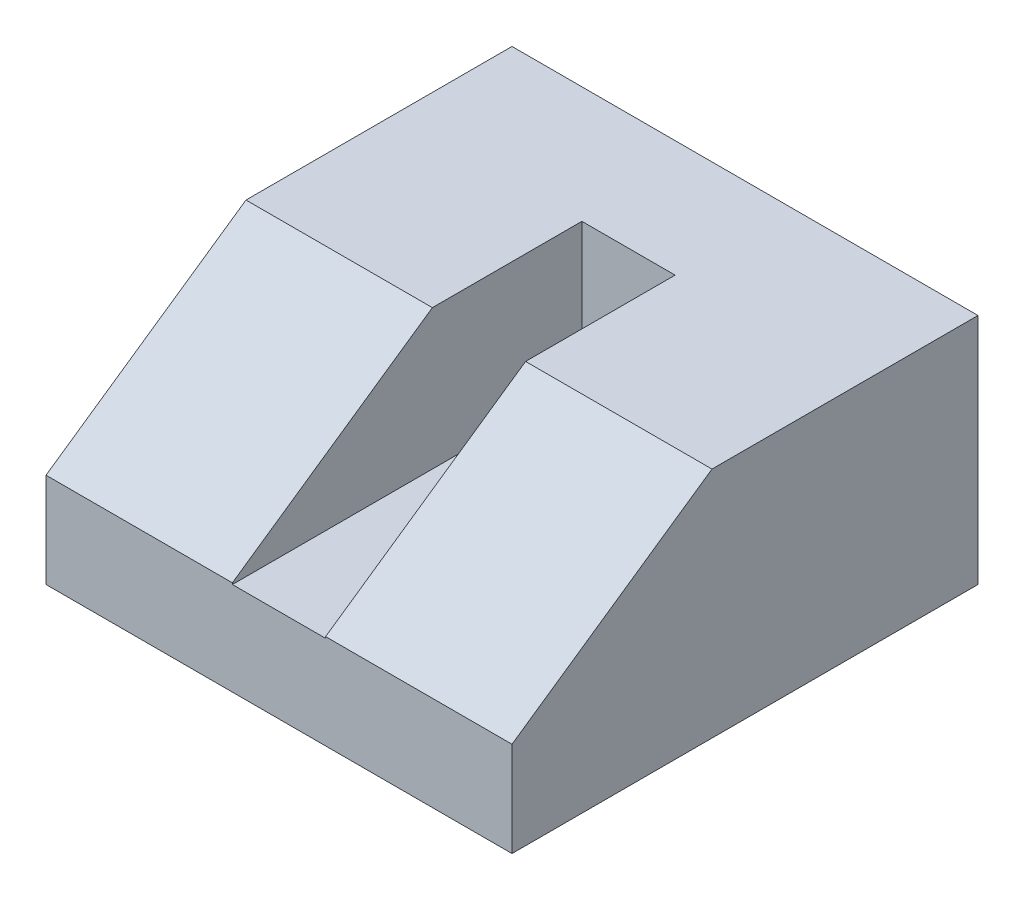
SolidWorks part; units mm, degrees
ref_plane "Front Plane" through (0, 0, 0) normal (0, 0, 1) x (1, 0, 0)
ref_plane "Top Plane" through (0, 0, 0) normal (0, 1, 0) x (1, 0, 0)
ref_plane "Right Plane" through (0, 0, 0) normal (1, 0, 0) x (0, 0, -1)
sketch "Sketch1" plane through (0, 0, 0) normal (0, 1, 0) x (1, 0, 0)
  circle A0 centre (0, 0) radius 25
  dimension "D1" = 50
extrude "Boss-Extrude1" add sketch "Sketch1" along normal blind 10
sketch "Sketch2" plane through (0, 10, 0) normal (0, 1, 0) x (1, 0, 0)
  line L1 (50, -50) -> (-50, -50)
  line L2 (50, -50) -> (50, 50)
  line L3 (50, 50) -> (-50, 50)
  line L4 (-50, -50) -> (-50, 50)
  line L5 (50, -50) -> (-50, 50) construction
  line L6 (50, 50) -> (-50, -50) construction
  point P0 (0, 0)
  dimension "D1" = 100
  dimension "D2" = 100
extrude "Boss-Extrude2" add sketch "Sketch2" along normal blind 50
sketch "Sketch4" plane through (-50, 0, 0) normal (-1, 0, 0) x (0, 0, 1)
  line L0 (50, 30.3188) -> (7.0855, 60)
  line L1 (50, 60) -> (50, 10) construction
  line L2 (-50, 60) -> (50, 60) construction
  line L3 (7.0855, 60) -> (50, 60)
  line L4 (50, 60) -> (50, 30.3188)
extrude "Cut-Extrude1" cut sketch "Sketch4" against normal through all
sketch "Sketch7" plane through (0, 60, 0) normal (0, 1, 0) x (1, 0, 0)
  line L0 (50, -50) -> (-50, -50) construction
  line L1 (-10, -50) -> (10, -50)
  line L2 (-10, -50) -> (-10, 25)
  line L3 (-10, 25) -> (10, 25)
  line L4 (10, -50) -> (10, 25)
  line L5 (0, -1000) -> (0, 49000) construction
  line L6 (50, 50) -> (-50, 50) construction
  dimension "D1" = 20
  dimension "D2" = 25
extrude "Cut-Extrude3" cut sketch "Sketch7" against normal blind 30
ref_point "Point1"
ref_point "Point2"
ref_axis "TurretAxis" through (-10, 42.984, 3.3423) along (1, 0, 0)
ref_axis "HeadAxis" through (0, 10, 0) along (0, -1, 0)
ref_point "HeadOrigin"
